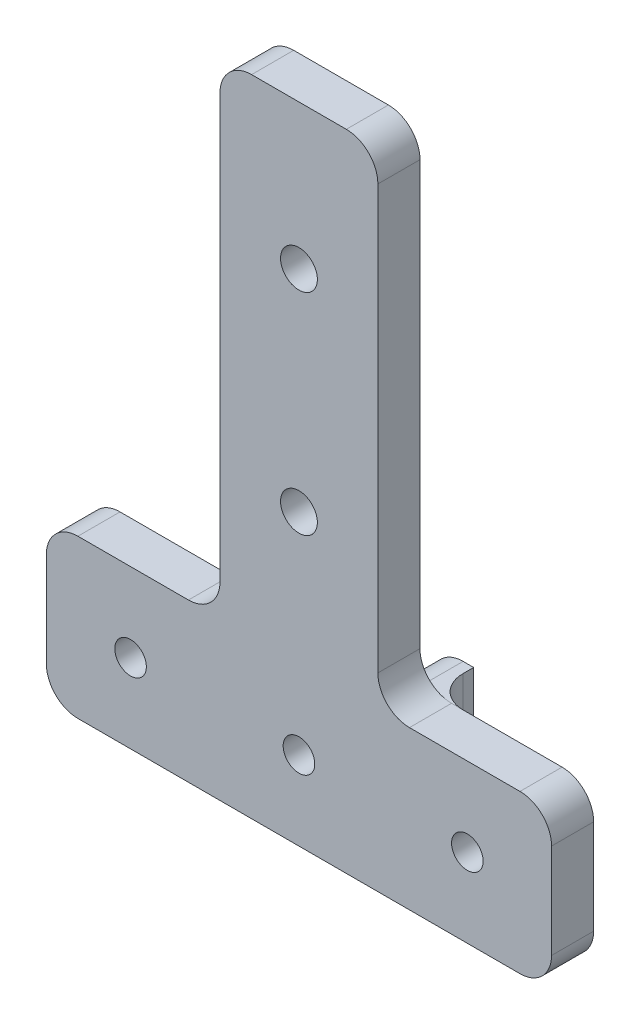
SolidWorks part; units mm, degrees
ref_plane "前视基准面" through (0, 0, 0) normal (0, 0, 1) x (1, 0, 0)
ref_plane "上视基准面" through (0, 0, 0) normal (0, 1, 0) x (1, 0, 0)
ref_plane "右视基准面" through (0, 0, 0) normal (1, 0, 0) x (0, 0, -1)
other "Configuration Table"
sketch "草图1" plane through (0, 0, 0) normal (0, 0, 1) x (1, 0, 0)
  line L0 (-49.7112, 0) -> (49.7112, 0) construction
  line L1 (0, 0) -> (0, 42.7175) construction
  line L2 (7.5, 7.5) -> (24, 7.5)
  line L3 (24, 7.5) -> (24, -7.5)
  line L4 (24, -7.5) -> (-24, -7.5)
  line L5 (7.5, 7.5) -> (7.5, 53.7328)
  line L6 (7.5, 53.7328) -> (-7.5, 53.7328)
  line L7 (-7.5, 7.5) -> (-7.5, 53.7328)
  line L8 (-24, 7.5) -> (-24, -7.5)
  line L9 (-7.5, 7.5) -> (-24, 7.5)
  line L10 (-24, 15.3135) -> (-21.6322, 15.3135)
  circle A0 centre (16, 0) radius 1.5
  circle A1 centre (0, 0) radius 1.5
  circle A2 centre (-16, 0) radius 1.5
  circle A3 centre (0, 20) radius 1.75
  circle A4 centre (0, 40) radius 1.75
  point P17 (0, 53.7328)
  point P19 (0, -7.5)
  dimension "D5" = 3
  dimension "D6" = 3
  dimension "D7" = 3.5
  dimension "D9" = 3.5
  dimension "D1" = 15
  dimension "D2" = 15
  dimension "D3" = 48
  dimension "D4" = 32
  dimension "D8" = 20
  dimension "D10" = 20
extrude "凸台-拉伸1" add sketch "草图1" along normal blind 4 contours L7 L9 L8 L4 L3 L2 L5 L6 A4 A3 A0 A1 A2 region at (0, 15.0432, 0)
fillet "圆角1" radius 3 8 edges at (-7.5, 53.7328, 2) (7.5, 53.7328, 2) (7.5, 7.5, 2) (24, 7.5, 2) (24, -7.5, 2) (-24, -7.5, 2) (-24, 7.5, 2) (-7.5, 7.5, 2)
sketch "草图2" plane through (0, 0, 0) normal (0, 0, -1) x (-1, 0, 0)
  line L0 (0, 0) -> (0, -11.5985) construction
  line L1 (-4.6, 7.5) -> (-4.6, -4.8362)
  line L2 (-4.6, -4.8362) -> (0, -4.8362)
  line L3 (-4.6, 7.5) -> (-0.6788, 7.5)
  line L4 (-4.6, 7.5) -> (-8.6, 7.5)
  line L5 (-10.5, 7.5) -> (-21, 7.5) construction
  line L6 (-8.6, 7.5) -> (-8.6, -7.5)
  line L7 (-21, -7.5) -> (21, -7.5) construction
  line L8 (-8.6, -7.5) -> (-4.6, -7.5)
  line L9 (-4.6, -7.5) -> (-4.6, -4.8362)
  line L10 (4.6, -7.5) -> (4.6, -4.8362)
  line L11 (8.6, -7.5) -> (4.6, -7.5)
  line L12 (8.6, 7.5) -> (8.6, -7.5)
  line L13 (4.6, 7.5) -> (8.6, 7.5)
  line L14 (4.6, 7.5) -> (4.6, -4.8362)
  line M13 (-21, -7.5) -> (21, -7.5)
  dimension "D1" = 9.2
  dimension "D2" = 4
extrude "凸台-拉伸2" add sketch "草图2" along normal blind 4 contours L13 L14 L10 L12 M13 | L9 L1 L4 L6 M13 region at (-6.6, 0, 0) region at (6.6, 0, 0)
fillet "圆角2" radius 3 2 edges at (-8.6, 0, 0) (8.6, 0, 0)
fillet "圆角3" radius 3 2 edges at (-4.6, 7.5, -2) (4.6, 7.5, -2)
